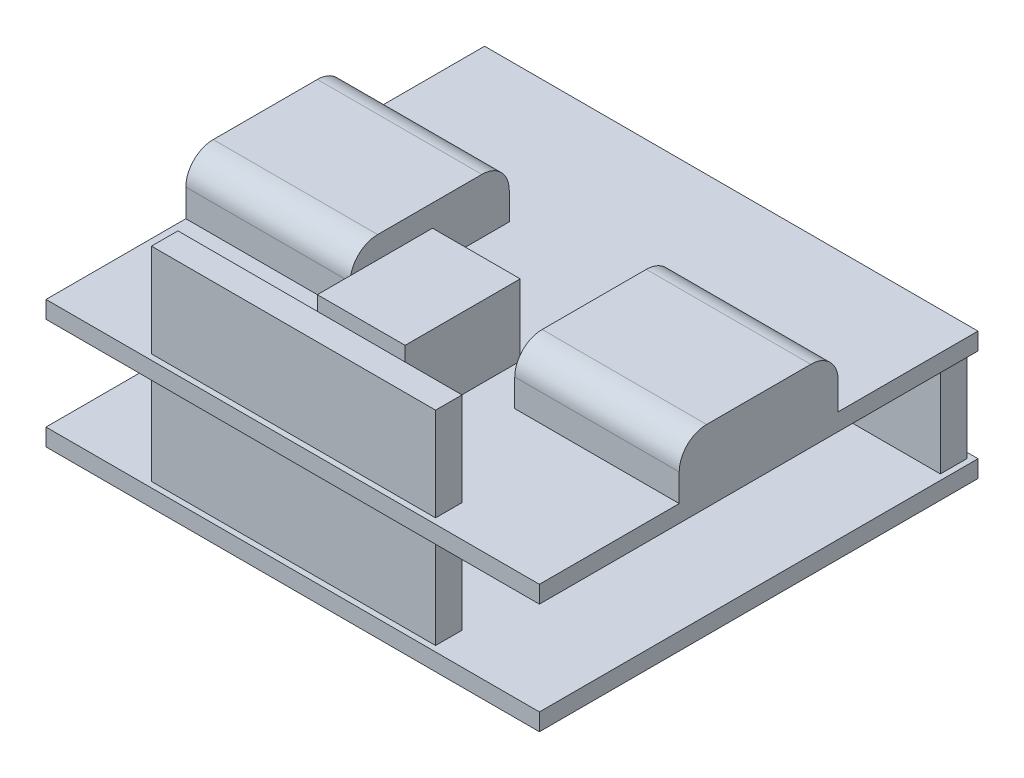
SolidWorks part; units mm, degrees
ref_plane "Front Plane" through (0, 0, 0) normal (0, 0, 1) x (1, 0, 0)
ref_plane "Top Plane" through (0, 0, 0) normal (0, 1, 0) x (1, 0, 0)
ref_plane "Right Plane" through (0, 0, 0) normal (1, 0, 0) x (0, 0, -1)
sketch "Sketch1" plane through (0, 0, 0) normal (0, 1, 0) x (1, 0, 0)
  line L1 (-22.5, -20) -> (22.5, -20)
  line L2 (-22.5, -20) -> (-22.5, 20)
  line L3 (-22.5, 20) -> (22.5, 20)
  line L4 (22.5, -20) -> (22.5, 20)
  line L5 (-22.5, -20) -> (22.5, 20) construction
  line L6 (-22.5, 20) -> (22.5, -20) construction
  point P0 (0, 0)
  dimension "D1" = 45
  dimension "D2" = 40
extrude "Boss-Extrude1" add sketch "Sketch1" along normal blind 1.57
sketch "Sketch2" plane through (0, 1.57, 0) normal (0, 1, 0) x (1, 0, 0)
  line L0 (-13.9, -20) -> (-13.9, 20) construction
  line L1 (21.99, 19.49) -> (-3.92, 19.49)
  line L2 (21.99, 19.49) -> (21.99, 17.08)
  line L3 (21.99, 17.08) -> (-3.92, 17.08)
  line L4 (-3.92, 19.49) -> (-3.92, 17.08)
  line L5 (12.52, -17.08) -> (-13.39, -17.08)
  line L6 (12.52, -17.08) -> (12.52, -19.49)
  line L7 (12.52, -19.49) -> (-13.39, -19.49)
  line L8 (-13.39, -17.08) -> (-13.39, -19.49)
  line L9 (-22.5, -20) -> (22.5, -20) construction
  line L10 (22.5, 20) -> (-22.5, 20) construction
  line L11 (22.5, -20) -> (22.5, 20) construction
  circle A0 centre (17.5, -15) radius 3.2 construction
  dimension "D6" = 6.4
  dimension "D1" = 2.41
  dimension "D2" = 2.41
  dimension "D3" = 25.91
  dimension "D4" = 25.91
  dimension "D5" = 36.4
  dimension "D7" = 5
  dimension "D8" = 5
  dimension "D9" = 0.51
  dimension "D10" = 0.51
  dimension "D11" = 0.51
  dimension "D12" = 0.51
extrude "Boss-Extrude2" add sketch "Sketch2" along normal blind 8.51
sketch "Sketch3" plane through (0, 10.08, 0) normal (0, 1, 0) x (1, 0, 0)
  line L0 (22.5, 20) -> (-22.5, 20) construction
  line L1 (22.5, -20) -> (-22.5, -20)
  line L2 (22.5, -20) -> (22.5, 20)
  line L3 (22.5, 20) -> (-22.5, 20)
  line L4 (-22.5, -20) -> (-22.5, 20)
  dimension "D1" = 45
extrude "Boss-Extrude3" add sketch "Sketch3" along normal blind 1.57
sketch "Sketch4" plane through (0, 11.65, 0) normal (0, 1, 0) x (1, 0, 0)
  line L0 (12.52, -17.08) -> (-13.39, -17.08)
  line L1 (12.52, -17.08) -> (12.52, -19.49)
  line L2 (12.52, -19.49) -> (-13.39, -19.49)
  line L3 (-13.39, -17.08) -> (-13.39, -19.49)
  line L4 (-22.5, -20) -> (22.5, -20) construction
  line L5 (22.5, -20) -> (22.5, 20) construction
  dimension "D1" = 0.51
  dimension "D2" = 2.41
  dimension "D3" = 25.91
  dimension "D4" = 9.98
extrude "Boss-Extrude4" add sketch "Sketch4" along normal blind 8.51
sketch "Sketch5" plane through (0, 11.65, 0) normal (0, 1, 0) x (1, 0, 0)
  line L0 (-22.5, 20) -> (-22.5, -20) construction
  line L1 (-22.5, -7.25) -> (-7.5, -7.25)
  line L2 (-22.5, -7.25) -> (-22.5, 7.25)
  line L3 (-22.5, 7.25) -> (-7.5, 7.25)
  line L4 (-7.5, -7.25) -> (-7.5, 7.25)
  line L5 (-11.088, 0) -> (11.088, 0) construction
  point P6 (-7.5, 0)
  dimension "D1" = 14.5
  dimension "D2" = 15
extrude "Boss-Extrude5" add sketch "Sketch5" along normal blind 5
fillet "Fillet1" radius 2.5 2 edges at (-15, 16.65, -7.25) (-15, 16.65, 7.25)
mirror "Mirror1" about plane through (0, 0, 0) normal (1, 0, 0) of "Fillet1", "Boss-Extrude5"
sketch "Sketch6" plane through (0, 11.65, 0) normal (0, 1, 0) x (1, 0, 0)
  line L0 (0, -11.088) -> (0, 11.088) construction
  line L1 (-4, -13.75) -> (4, -13.75)
  line L2 (-4, -13.75) -> (-4, -3.25)
  line L3 (-4, -3.25) -> (4, -3.25)
  line L4 (4, -13.75) -> (4, -3.25)
  line L5 (-11.088, 0) -> (11.088, 0) construction
  point P4 (0, -13.75)
  point P7 (-4, -8.5)
  dimension "D1" = 8
  dimension "D2" = 10.5
  dimension "D3" = 8.5
extrude "Boss-Extrude6" add sketch "Sketch6" along normal blind 6.5
